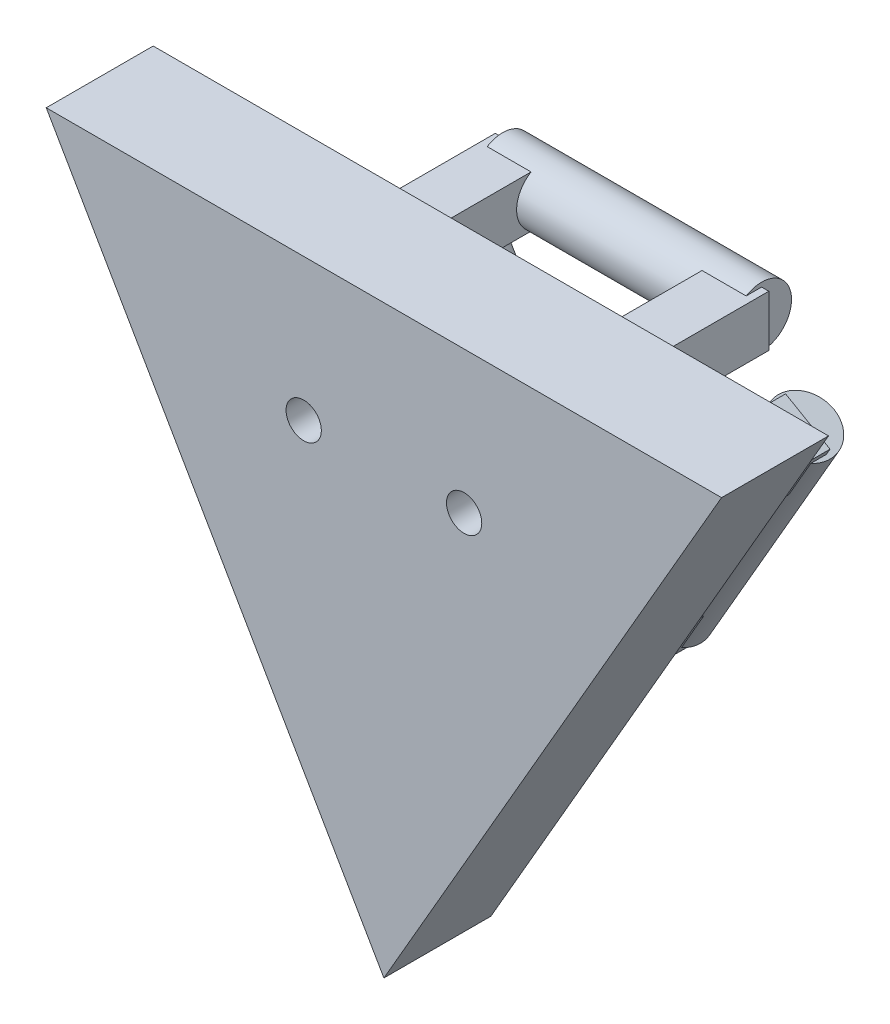
SolidWorks part; units mm, degrees
ref_plane "前视基准面" through (0, 0, 0) normal (0, 0, 1) x (1, 0, 0)
ref_plane "上视基准面" through (0, 0, 0) normal (0, 1, 0) x (1, 0, 0)
ref_plane "右视基准面" through (0, 0, 0) normal (1, 0, 0) x (0, 0, -1)
sketch "草图1" plane through (0, 0, 0) normal (0, 0, 1) x (1, 0, 0)
  line L0 (0, 0) -> (0, 14.4)
  line L1 (0, 0) -> (10.0459, 5.8)
  line L2 (0, 0) -> (-10.0459, -5.8)
  line L3 (0, 0) -> (10.0459, -5.8)
  line L4 (0, 0) -> (-10.0459, 5.8)
  line L5 (0, 0) -> (0, -16.428)
  line L6 (0, -36.4056) -> (31.5724, 18.2793)
  line L7 (10.3923, 14.4) -> (-10.3923, 14.4)
  line L8 (7.9905, 14.0025) -> (12.7905, 14.0025)
  line L9 (-12.7905, 13.9975) -> (-7.9905, 13.9975)
  line L10 (-12.7905, 13.9975) -> (-12.7905, 9.1975)
  line L11 (-12.7905, 9.1975) -> (-7.9905, 9.1975)
  line L12 (-7.9905, 13.9975) -> (-7.9905, 9.1975)
  line L13 (-12.7905, 13.9975) -> (-7.9905, 9.1975) construction
  line L14 (-12.7905, 9.1975) -> (-7.9905, 13.9975) construction
  line L15 (7.9905, 14.0025) -> (7.9905, 9.2025)
  line L16 (7.9905, 9.2025) -> (12.7905, 9.2025)
  line L17 (12.7905, 14.0025) -> (12.7905, 9.2025)
  line L18 (7.9905, 14.0025) -> (12.7905, 9.2025) construction
  line L19 (7.9905, 9.2025) -> (12.7905, 14.0025) construction
  line L20 (-16.1217, -0.0813) -> (-18.5217, 4.0756)
  line L21 (-5.727, -18.0756) -> (-8.127, -13.9187)
  line L22 (-5.727, -18.0756) -> (-1.5701, -15.6756)
  line L23 (-1.5701, -15.6756) -> (-3.9701, -11.5187)
  line L24 (-8.127, -13.9187) -> (-3.9701, -11.5187)
  line L25 (-5.727, -18.0756) -> (-3.9701, -11.5187) construction
  line L26 (-1.5701, -15.6756) -> (-8.127, -13.9187) construction
  line L27 (-16.1217, -0.0813) -> (-11.9648, 2.3187)
  line L28 (-11.9648, 2.3187) -> (-14.3648, 6.4756)
  line L29 (-18.5217, 4.0756) -> (-14.3648, 6.4756)
  line L30 (-16.1217, -0.0813) -> (-14.3648, 6.4756) construction
  line L31 (-11.9648, 2.3187) -> (-18.5217, 4.0756) construction
  line L32 (8.1313, -13.9212) -> (5.7313, -18.0781)
  line L33 (18.5174, 4.0781) -> (16.1174, -0.0788)
  line L34 (18.5174, 4.0781) -> (14.3605, 6.4781)
  line L35 (14.3605, 6.4781) -> (11.9605, 2.3212)
  line L36 (16.1174, -0.0788) -> (11.9605, 2.3212)
  line L37 (18.5174, 4.0781) -> (11.9605, 2.3212) construction
  line L38 (14.3605, 6.4781) -> (16.1174, -0.0788) construction
  line L39 (8.1313, -13.9212) -> (3.9743, -11.5212)
  line L40 (3.9743, -11.5212) -> (1.5743, -15.6781)
  line L41 (5.7313, -18.0781) -> (1.5743, -15.6781)
  line L42 (8.1313, -13.9212) -> (1.5743, -15.6781) construction
  line L43 (3.9743, -11.5212) -> (5.7313, -18.0781) construction
  line L44 (0, -36.4056) -> (-31.5724, 18.2793)
  line L45 (-31.5724, 18.2793) -> (31.5724, 18.2793)
  line L46 (15.239, 3.1996) -> (4.8528, -14.7996)
  line L47 (-15.5897, 2.9972) -> (-5.1949, -14.9972)
  line L48 (-10.3923, 12) -> (10.3886, 12.005)
  circle A0 centre (0, 0) radius 40
  circle A1 centre (0, 0) radius 10
  circle A2 centre (0, 0) radius 11.6
extrude "凸台-拉伸1" add sketch "草图1" along normal blind 10 contours A0 A2 L12 L11 L10 L9 L15 L8 L17 L16 L32 L41 L40 L39 L33 L36 L35 L34 L20 L29 L28 L27 L21 L24 L23 L22 | L3 A2 L1 A1 | L3 A1 L1 | L5 A1 L3 | L5 A2 L3 A1 | L2 A1 L5 | L2 A2 L5 A1 | L4 A1 L2 | L4 A2 L2 A1 | L0 A1 L4 | L1 A1 L0 | L0 A2 L4 A1 | L1 A2 L0 A1 | L17 L8 L15 L16 | L12 L9 L10 L11 | L29 L20 L27 L28 | L24 L21 L22 L23 | L41 L32 L39 L40 | L36 L33 L34 L35 region at (-3.1831, 5.5133, 0) region at (3.1831, 5.5133, 0) region at (-3.1831, -5.5133, 0) region at (6.3662, 0, 0) region at (-6.3662, 0, 0) region at (3.1831, -5.5133, 0) region at (-5.1661, 8.9479, 0) region at (5.1661, 8.9479, 0) region at (13.0464, 1.8013, 0) region at (10.3321, 0, 0) region at (-5.1661, -8.9479, 0) region at (-10.3321, 0, 0) region at (5.1661, -8.9479, 0) region at (-10.3905, 11.5975, 0) region at (10.3905, 11.6025, 0) region at (7.0454, -13.4013, 0) region at (-15.0628, -8.6455, 0) region at (-4.8485, -14.7972, 0) region at (-15.2433, 3.1972, 0)
extrude "凸台-拉伸2" add sketch "草图1<5>" against normal blind 13.2 contours L12 L9 L10 L11 | L29 L20 L27 L28 | L24 L21 L22 L23 | L32 L41 L40 L39 | L17 L16 L15 L8 | L33 L36 L35 L34 region at (-10.3905, 11.5975, 0) region at (-4.8485, -14.7972, 0) region at (-15.2433, 3.1972, 0)
sketch "草图1<5>" plane through (0, 0, 0) normal (0, 0, 1) x (1, 0, 0) same geometry as "草图1"
sketch "草图3" plane through (3.9952, -6.9199, 0) normal (-0.5, 0.866, 0) x (0.866, 0.5, 0)
  line L0 (-14.0025, 13.2) -> (-9.2025, 13.2) construction
  circle A0 centre (-11.6025, 13.2) radius 2.8
extrude "凸台-拉伸3" add sketch "草图3" along normal blind 20.1058 and the other way blind 4
sketch "草图4" plane through (-7.9905, 0, 0) normal (1, 0, 0) x (0, 0, -1)
  line L0 (13.2, 14.0025) -> (13.2, 9.2025) construction
  circle A0 centre (13.2, 11.6025) radius 2.8
extrude "凸台-拉伸4" add sketch "草图4" along normal blind 20.1058 and the other way blind 4.1058
sketch "草图5" plane through (3.9952, 6.9199, 0) normal (-0.5, -0.866, 0) x (-0.866, 0.5, 0)
  line L0 (-14.0025, 13.2) -> (-9.2025, 13.2) construction
  circle A0 centre (-11.6025, 13.2) radius 2.8
extrude "凸台-拉伸5" add sketch "草图5" along normal blind 20.1058 and the other way blind 4.1058
sketch "草图6" plane through (0, 0, 10) normal (0, 0, 1) x (1, 0, 0)
  line L0 (0, 0) -> (0, 5)
  line L5 (0, 5) -> (-7.5, 5)
  line L6 (-7.5, 5) -> (7.5, 5)
hole_wizard "M4 螺纹孔1" positions "草图7" profile "草图8" tap size "M4" standard "GB"
sketch "草图7" plane through (0, 0, 10) normal (0, 0, 1) x (1, 0, 0)
  point P0 (7.5, 5)
  point P3 (-7.5, 5)
sketch "草图8" plane through (7.5, 5, 10) normal (1, 0, 0) x (0, -1, 0)
  line L0 (0, 0) -> (0, 11.0914)
  line L1 (0, 11.0914) -> (1.65, 10.1)
  line L2 (1.65, 10.1) -> (1.65, 0)
  line L5 (1.65, 0) -> (0, 0)
  line L10 (0, 11.0914) -> (-1.65, 10.1) construction
  line L11 (0, -6.35) -> (0, 107.95) construction
  dimension "螺纹孔钻头直径" = 3.3
  dimension "螺纹孔钻头深度" = 10.1
  dimension "导头角度" = 118
cosmetic thread "孔螺蚊线1" parameters "D1"=8, "D2"=4
cosmetic thread "孔螺蚊线2" parameters "D1"=8, "D2"=4
